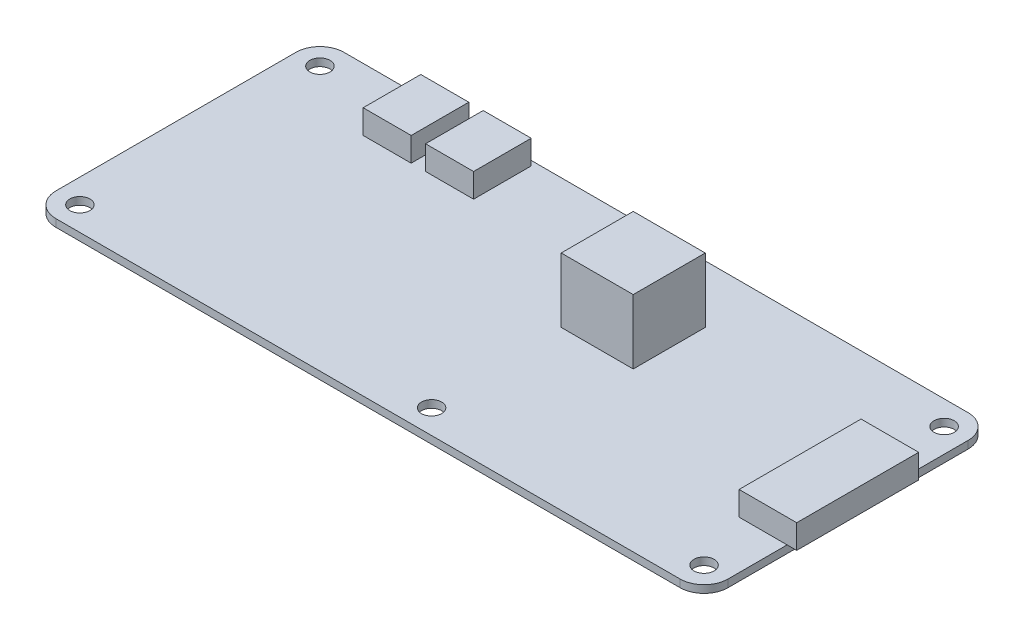
SolidWorks part; units mm, degrees
ref_plane "Front Plane" through (0, 0, 0) normal (0, 0, 1) x (1, 0, 0)
ref_plane "Top Plane" through (0, 0, 0) normal (0, 1, 0) x (1, 0, 0)
ref_plane "Right Plane" through (0, 0, 0) normal (1, 0, 0) x (0, 0, -1)
sketch "Sketch2" plane through (0, 0, 0) normal (0, 1, 0) x (1, 0, 0)
  line L0 (0, 55) -> (140, 55) construction
  line L1 (5, 0) -> (135, 0)
  line L2 (0, 5) -> (0, 55)
  line L3 (5, 60) -> (135, 60)
  line L4 (140, 5) -> (140, 55)
  line L5 (140, 5) -> (0, 5) construction
  arc A0 (0, 5) -> (5, 0) centre (5, 5) ccw
  arc A1 (140, 55) -> (135, 60) centre (135, 55) ccw
  arc A2 (135, 0) -> (140, 5) centre (135, 5) ccw
  arc A3 (5, 60) -> (0, 55) centre (5, 55) ccw
  circle A4 centre (5, 55) radius 2.1
  circle A5 centre (5, 5) radius 2.1
  circle A6 centre (135, 5) radius 2.1
  circle A7 centre (135, 55) radius 2.1
  circle A8 centre (78.25, 55) radius 2.1
  circle A9 centre (78.25, 5) radius 2.1
  point P7 (0, 0)
  point P10 (140, 60)
  point P15 (0, 60)
  dimension "D3" = 5
  dimension "D5" = 4.2
  dimension "D1" = 60
  dimension "D2" = 140
  dimension "D4" = 78.25
extrude "Boss-Extrude1" add sketch "Sketch2" along normal blind 1.5748
sketch "Sketch3" plane through (0, 1.5748, 0) normal (0, 1, 0) x (1, 0, 0)
  line L0 (140, 30) -> (142, 30) construction
  line L1 (130, 42.7) -> (142, 42.7)
  line L2 (130, 42.7) -> (130, 17.3)
  line L3 (130, 17.3) -> (142, 17.3)
  line L4 (142, 42.7) -> (142, 17.3)
  line L5 (0, 55) -> (0, 5) construction
  line L6 (140, 5) -> (140, 55) construction
  line L7 (35, 59) -> (45, 59)
  line L8 (22, 59) -> (32, 59)
  line L9 (22, 59) -> (22, 47)
  line L10 (22, 47) -> (32, 47)
  line L11 (32, 59) -> (32, 47)
  line L12 (35, 59) -> (35, 47)
  line L13 (35, 47) -> (45, 47)
  line L14 (45, 59) -> (45, 47)
  line L15 (135, 60) -> (5, 60) construction
  dimension "D1" = 2
  dimension "D2" = 25.4
  dimension "D3" = 12
  dimension "D4" = 22
  dimension "D5" = 3
  dimension "D6" = 1
  dimension "D7" = 12
  dimension "D8" = 10
extrude "Boss-Extrude2" add sketch "Sketch3" along normal blind 5 contours L4 L3 L2 L1 | L9 L8 L11 L10 | L12 L7 L14 L13
sketch "Sketch5" plane through (0, 1.5748, 0) normal (0, 1, 0) x (1, 0, 0)
  line L0 (135, 60) -> (5, 60) construction
  line L1 (77.25, 48) -> (92.25, 48)
  line L2 (77.25, 48) -> (77.25, 33)
  line L3 (77.25, 33) -> (92.25, 33)
  line L4 (92.25, 48) -> (92.25, 33)
  circle A1 centre (78.25, 55) radius 2.1 construction
  dimension "D1" = 12
  dimension "D2" = 15
  dimension "D3" = 1
extrude "Boss-Extrude3" add sketch "Sketch5" along normal offset from surface (13.4252 mm away) 15 up to face at (70, 0, -30) offset beyond the face yes
